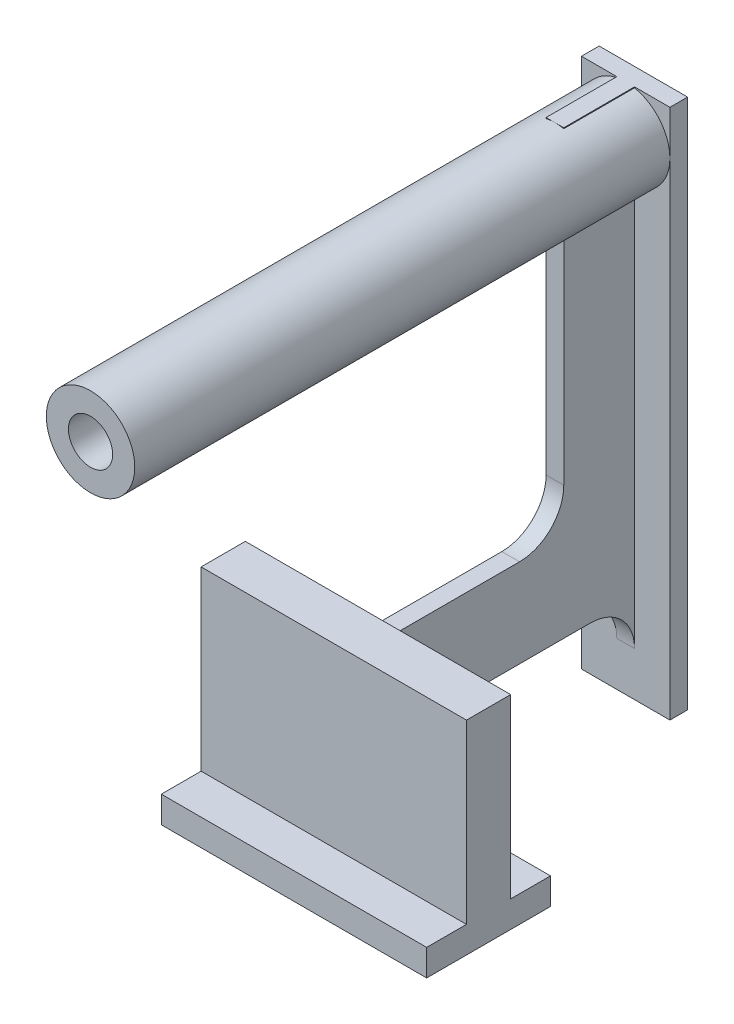
SolidWorks part; units mm, degrees
ref_plane "Front Plane" through (0, 0, 0) normal (0, 0, 1) x (1, 0, 0)
ref_plane "Top Plane" through (0, 0, 0) normal (0, 1, 0) x (1, 0, 0)
ref_plane "Right Plane" through (0, 0, 0) normal (1, 0, 0) x (0, 0, -1)
sketch "Sketch1" plane through (0, 0, 0) normal (1, 0, 0) x (0, 0, -1)
  line L0 (0, -17.2999) -> (0, 38.275) construction
  line L1 (-7, 1.5) -> (7, 1.5)
  line L2 (-7, 1.5) -> (-7, -1.5)
  line L3 (-7, -1.5) -> (7, -1.5)
  line L4 (7, 1.5) -> (7, -1.5)
  line L5 (-7, 1.5) -> (7, -1.5) construction
  line L6 (-7, -1.5) -> (7, 1.5) construction
  line L8 (-2.5, 21.5) -> (2.5, 21.5)
  line L9 (-2.5, 21.5) -> (-2.5, 1.5)
  line L10 (-2.5, 1.5) -> (2.5, 1.5)
  line L11 (2.5, 21.5) -> (2.5, 1.5)
  line L12 (-2.5, 21.5) -> (2.5, 1.5) construction
  line L13 (-2.5, 1.5) -> (2.5, 21.5) construction
  point P0 (0, 0)
  point P1 (0, 0)
  point P9 (0, 11.5)
  dimension "D1" = 5
  dimension "D2" = 20
  dimension "D3" = 14
  dimension "D4" = 3
extrude "Boss-Extrude1" add sketch "Sketch1" along normal blind 30 contours L11 L8 L9 L1 | L4 L1 L2 L3 region at (0, 0, 0) region at (0, 11.5, 0)
sketch "Sketch2" plane through (0, 0, 0) normal (0, 0, 1) x (1, 0, 0)
  line L0 (15, 1.5) -> (15, 32.2821) construction
  line L1 (30, 1.5) -> (0, 1.5) construction
  line L2 (0, 0) -> (39.1823, 0) construction
  circle A0 centre (15, 55) radius 5
  circle A1 centre (15, 55) radius 2.5
  point P4 (15, 55)
  dimension "D1" = 55
  dimension "D2" = 5
  dimension "D3" = 10
sketch "Sketch4" plane through (0, 0, 0) normal (0, 1, 0) x (1, 0, 0)
  line L0 (15, 0) -> (15, 14.6802) construction
  line L1 (30, 2.5) -> (0, 2.5) construction
  line L2 (14, 32.5) -> (16, 32.5)
  line L3 (14, 32.5) -> (14, 2.5)
  line L4 (14, 2.5) -> (16, 2.5)
  line L5 (16, 32.5) -> (16, 2.5)
  line L6 (14, 32.5) -> (16, 2.5) construction
  line L7 (14, 2.5) -> (16, 32.5) construction
  line L8 (15, 14.6802) -> (15, 36.8844) construction
  line L9 (14, 22.5) -> (16, 22.5)
  line L10 (10, 30.5) -> (20, 30.5)
  line L11 (10, 30.5) -> (10, 32.5)
  line L12 (10, 32.5) -> (20, 32.5)
  line L13 (20, 30.5) -> (20, 32.5)
  line L14 (10, 30.5) -> (20, 32.5) construction
  line L15 (10, 32.5) -> (20, 30.5) construction
  point P3 (15, 17.5)
  point P10 (15, 31.5)
  point P12 (15, 31.5)
  point P17 (15, 2.5)
  dimension "D1" = 2
  dimension "D2" = 30
  dimension "D3" = 29
  dimension "D4" = 2
  dimension "D5" = 10
  dimension "D6" = 20
extrude "Boss-Extrude2" add sketch "Sketch4" along normal blind 60 separate body contours L10 L13 L12 L5 | L3 L10 L5 L2 | L12 L11 L10 L3 | L10 L3 L9 L5 region at (15, 0, -31.5) region at (12, 0, -31.5) region at (18, 0, -31.5) region at (15, 0, -26.5)
extrude "Boss-Extrude3" add sketch "Sketch4<4>" along normal blind 20 contours L9 L3 L4 L5 region at (15, 0, -12.5)
sketch "Sketch4<4>" plane through (0, 0, 0) normal (0, 1, 0) x (1, 0, 0) same geometry as "Sketch4"
extrude "Cut-Extrude1" cut sketch "Sketch4<5>" along normal blind 10 contours L10 L3 L9 L5 | L9 L3 L4 L5 region at (15, 0, -26.5) region at (15, 0, -12.5)
sketch "Sketch4<5>" plane through (0, 0, 0) normal (0, 1, 0) x (1, 0, 0) same geometry as "Sketch4"
extrude "Boss-Extrude4" add sketch "Sketch2" along normal blind 30 and the other way up to surface (32.5 mm away) contours A0 A1 region at (10.1414, 55, 0) other way up to face at (15, 30, -32.5)
fillet "Fillet1" radius 5 2 edges at (15, 10, -30.5) (15, 20, -22.5)
